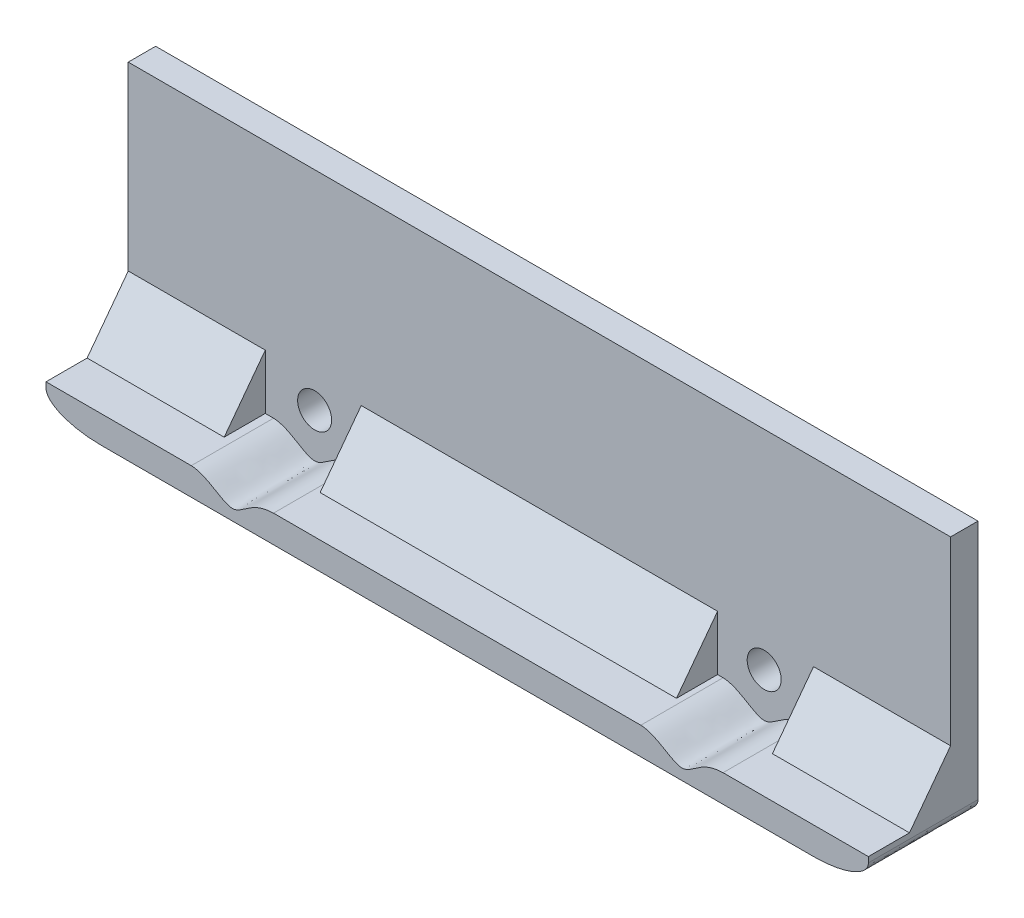
SolidWorks part; units mm, degrees
ref_plane "Front Plane" through (0, 0, 0) normal (0, 0, 1) x (1, 0, 0)
ref_plane "Top Plane" through (0, 0, 0) normal (0, 1, 0) x (1, 0, 0)
ref_plane "Right Plane" through (0, 0, 0) normal (1, 0, 0) x (0, 0, -1)
sketch "Sketch1" plane through (0, 0, 0) normal (0, 0, 1) x (1, 0, 0)
  line L0 (11, 0) -> (-11, 0) construction
  line L1 (-75, 0) -> (75, 0)
  line L2 (-75, 0) -> (-75, 48)
  line L3 (-75, 48) -> (75, 48)
  line L4 (75, 0) -> (75, 48)
  line L5 (0, 70.9447) -> (0, -59.6077) construction
  circle A0 centre (-41, 10) radius 3.1
  circle A1 centre (41, 10) radius 3.1
  point P12 (0, 0)
  point P13 (-132.3209, 64.9817)
  dimension "D4" = 6.2
  dimension "D5" = 6.2
  dimension "D1" = 150
  dimension "D2" = 82
  dimension "D3" = 10
  dimension "D6" = 48
extrude "Boss-Extrude1" add sketch "Sketch1" along normal blind 5
sketch "Sketch2" plane through (0, 0, 0) normal (0, 0, 1) x (1, 0, 0)
  line L0 (11, 0) -> (-11, 0) construction
  line L1 (-75, 0) -> (75, 0)
  line L2 (-75, 0) -> (-75, 5)
  line L3 (-75, 5) -> (75, 5)
  line L4 (75, 0) -> (75, 5)
  line L5 (75, 0) -> (75, 48) construction
  line L6 (-41, 13.1) -> (-41, 6.9) construction
  line L7 (41, 13.1) -> (41, 6.9) construction
  circle A0 centre (-41, 10) radius 3.1 construction
  circle A1 centre (41, 10) radius 3.1 construction
  spline S0 degree 3 poles (-48.5, 5) (-45.5232, 4.8951) (-40.329, -0.8951) (-37.8188, 4.8951) (-33.5, 5) knots 0 0 0 0 0.5 1 1 1 1
  spline S1 degree 3 poles (33.5, 5) (36.4768, 4.8951) (41.671, -0.8951) (44.1812, 4.8951) (48.5, 5) knots 0 0 0 0 0.5 1 1 1 1
  point P10 (0, 0)
  point P17 (0, 0)
  point P18 (0, 0)
  point P27 (0, 0)
  point P28 (0, 0)
  dimension "D1" = 5
  dimension "D2" = 150
  dimension "D3" = 3
  dimension "D4" = 15
  dimension "D5" = 15
  dimension "D6" = 3
extrude "Boss-Extrude2" add sketch "Sketch2" along normal blind 20 contours S0 L3 L2 L1 L4 region at (0.0128, 2.4201, 0)
sketch "Sketch4" plane through (-75, 0, 0) normal (-1, 0, 0) x (0, 0, 1)
  line L0 (5, 5) -> (12.5, 5)
  line L1 (20, 5) -> (5, 5) construction
  line L2 (12.5, 5) -> (5, 15)
  line L3 (5, 15) -> (5, 5)
  point P5 (12.5, 5)
  dimension "D1" = 7.5
  dimension "D2" = 10
extrude "Boss-Extrude3" add sketch "Sketch4" against normal blind 25
extrude "Boss-Extrude4" add sketch "Sketch4<2>" along normal blind 25 from surface starting at face at (75, 17.6667, 8.3333)
sketch "Sketch4<2>" plane through (-75, 0, 0) normal (-1, 0, 0) x (0, 0, 1) same geometry as "Sketch4"
extrude "Boss-Extrude5" add sketch "Sketch4<3>" along normal mid plane 65 from surface starting at plane "Right Plane"
sketch "Sketch4<3>" plane through (-75, 0, 0) normal (-1, 0, 0) x (0, 0, 1) same geometry as "Sketch4"
fillet "Fillet5" radius 4 1 edges at (-75, 0, 10) second distance 10 first distance on face at (-75, 17.2857, 8.9286)
fillet "Fillet6" radius 10 1 edges at (75, 0, 10) second distance 4 first distance on face at (-30, 0, 12.5)
